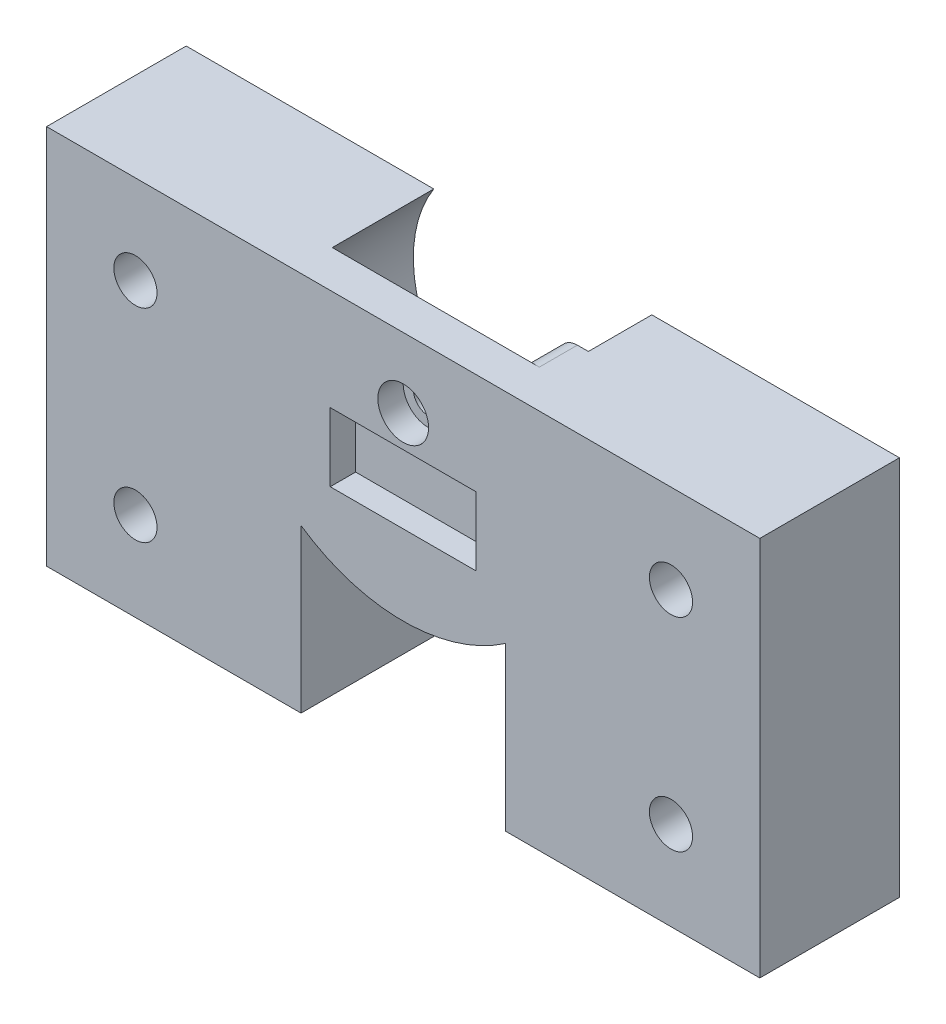
SolidWorks part; units mm, degrees
ref_plane "Front Plane" through (0, 0, 0) normal (0, 0, 1) x (1, 0, 0)
ref_plane "Top Plane" through (0, 0, 0) normal (0, 1, 0) x (1, 0, 0)
ref_plane "Right Plane" through (0, 0, 0) normal (1, 0, 0) x (0, 0, -1)
sketch "Sketch1" plane through (0, 0, 0) normal (0, 0, 1) x (1, 0, 0)
  line L0 (19.5099, 0) -> (0, 0)
  line L1 (28.1, -5.5) -> (28.1, -10) construction
  line L2 (0, 0) -> (0, -30)
  line L3 (0, -30) -> (56.2, -30)
  line L4 (36.6901, 0) -> (56.2, 0)
  line L5 (56.2, 0) -> (56.2, -30)
  line L6 (19.5099, 0) -> (36.6901, 0) construction
  line L7 (35.8259, 0) -> (36.6901, 0)
  line L8 (35.8259, -3) -> (37.9889, -3)
  line L18 (0, -15) -> (56.2, -15) construction
  arc A0 (19.5099, 0) -> (37.9889, -3) centre (28.1, -5.5) ccw
  arc A1 (35.8259, 0) -> (35.8259, -3) centre (35.8259, -1.5) ccw
  dimension "D4" = 30
  dimension "D5" = 1.5
  dimension "D2" = 5.5
  dimension "D1" = 10.2
  dimension "D3" = 56.2
extrude "Boss-Extrude1" add sketch "Sketch1" along normal blind 8
sketch "Sketch2" [suppressed] plane through (0, 0, 0) normal (0, 0, -1) x (-1, 0, 0)
  line L0 (-56.2, -15) -> (0, -15) construction
  line L1 (-56.2, -30) -> (-56.2, 0) construction
  line L2 (-46.0015, -7) -> (-47.6007, -4.23)
  line L3 (-47.6007, -4.23) -> (-50.7993, -4.23)
  line L4 (-50.7993, -4.23) -> (-52.3985, -7)
  line L5 (-52.3985, -7) -> (-50.7993, -9.77)
  line L6 (-50.7993, -9.77) -> (-47.6007, -9.77)
  line L7 (-47.6007, -9.77) -> (-46.0015, -7)
  line L8 (0, 0) -> (0, -30) construction
  line L9 (-8.5993, -9.77) -> (-10.1985, -7)
  line L10 (-28.1, 0) -> (-28.1, -30) construction
  line L11 (0, -30) -> (-56.2, -30) construction
  line L12 (-5.4007, -9.77) -> (-8.5993, -9.77)
  line L13 (-3.8015, -7) -> (-5.4007, -9.77)
  line L14 (-5.4007, -4.23) -> (-3.8015, -7)
  line L15 (-8.5993, -4.23) -> (-5.4007, -4.23)
  line L16 (-10.1985, -7) -> (-8.5993, -4.23)
  line L17 (-10.1985, -23) -> (-8.5993, -25.77)
  line L18 (-8.5993, -25.77) -> (-5.4007, -25.77)
  line L19 (-5.4007, -25.77) -> (-3.8015, -23)
  line L20 (-3.8015, -23) -> (-5.4007, -20.23)
  line L21 (-5.4007, -20.23) -> (-8.5993, -20.23)
  line L22 (-8.5993, -20.23) -> (-10.1985, -23)
  line L23 (-47.6007, -20.23) -> (-46.0015, -23)
  line L24 (-50.7993, -20.23) -> (-47.6007, -20.23)
  line L25 (-52.3985, -23) -> (-50.7993, -20.23)
  line L26 (-50.7993, -25.77) -> (-52.3985, -23)
  line L27 (-47.6007, -25.77) -> (-50.7993, -25.77)
  line L28 (-46.0015, -23) -> (-47.6007, -25.77)
  circle A0 centre (-49.2, -7) radius 2.77 construction
  circle A1 centre (-7, -7) radius 2.77 construction
  circle A2 centre (-7, -23) radius 2.77 construction
  circle A3 centre (-49.2, -23) radius 2.77 construction
  dimension "D1" = 5.54
  dimension "D2" = 7
  dimension "D3" = 7
extrude "Cut-Extrude1" [suppressed] cut sketch "Sketch2" against normal blind 2.4
sketch "Sketch3" plane through (0, 0, 8) normal (0, 0, 1) x (1, 0, 0)
  line L0 (0, 0) -> (0, -30)
  line L1 (0, -30) -> (56.2, -30)
  line L2 (56.2, -30) -> (56.2, 0) construction
  line L3 (56.2, -30) -> (56.2, 0)
  line L4 (0, 0) -> (56.2, 0)
extrude "Boss-Extrude2" add sketch "Sketch3" along normal blind 3
sketch "Sketch4" plane through (0, 0, 0) normal (0, 0, -1) x (-1, 0, 0)
  line L0 (-56.2, -15) -> (0, -15) construction
  line L1 (-56.2, -30) -> (-56.2, 0) construction
  line L2 (0, 0) -> (0, -30) construction
  line L3 (-28.1, -5.5) -> (-28.1, -30) construction
  line L8 (0, -30) -> (-56.2, -30) construction
  circle A0 centre (-49.2, -7) radius 1.7
  circle A1 centre (-7, -7) radius 1.7
  circle A2 centre (-7, -23) radius 1.7
  circle A3 centre (-49.2, -23) radius 1.7
  circle A4 centre (-28.1, -5.5) radius 1.2
  arc A5 (-37.9889, -3) -> (-19.5099, 0) centre (-28.1, -5.5) ccw construction
  dimension "D1" = 3.4
  dimension "D4" = 2.4
  dimension "D2" = 7
  dimension "D3" = 7
extrude "Cut-Extrude2" cut sketch "Sketch4" against normal up to surface (11 mm away) up to face at (28.1, -15, 11)
sketch "Sketch5" plane through (0, 0, 0) normal (0, 0, -1) x (-1, 0, 0)
  line L0 (-19.5099, 0) -> (-36.6901, 0)
  line L1 (-56.2, 0) -> (-35.8259, 0) construction
  arc A0 (-36.6901, 0) -> (-19.5099, 0) centre (-28.1, -5.5) ccw
extrude "Cut-Extrude3" cut sketch "Sketch5" against normal blind 5
sketch "Sketch7" plane through (0, 0, 11) normal (0, 0, 1) x (1, 0, 0)
  line L0 (28.1, -5.5) -> (28.1, -30) construction
  line L1 (22.35, -8) -> (33.85, -8)
  line L2 (22.35, -8) -> (22.35, -13.4)
  line L3 (22.35, -13.4) -> (33.85, -13.4)
  line L4 (33.85, -8) -> (33.85, -13.4)
  line L5 (0, -30) -> (56.2, -30) construction
  circle A0 centre (28.1, -5.5) radius 2
  point P7 (0, 0)
  dimension "D1" = 4
  dimension "D2" = 5.75
  dimension "D3" = 5.4
  dimension "D4" = 8
  dimension "D5" = 5.75
extrude "Cut-Extrude4" cut sketch "Sketch7" against normal blind 2
sketch "Sketch8" plane through (0, 0, 11) normal (0, 0, 1) x (1, 0, 0)
  line L0 (28.1, 0) -> (28.1, -30) construction
  line L1 (56.2, 0) -> (0, 0) construction
  line L2 (0, -30) -> (56.2, -30) construction
  line L3 (0, -15) -> (56.2, -15) construction
  line L4 (0, 0) -> (0, -30) construction
  line L5 (56.2, -30) -> (56.2, 0) construction
  circle A0 centre (7, -7) radius 2.875
  circle A1 centre (49.2, -7) radius 2.875
  circle A2 centre (49.2, -23) radius 2.875
  circle A3 centre (7, -23) radius 2.875
  dimension "D1" = 5.75
extrude "Cut-Extrude5" [suppressed] cut sketch "Sketch8" against normal blind 3
sketch "Sketch9" plane through (0, 0, 0) normal (0, 0, 1) x (1, 0, 0)
  line L0 (23, -30) -> (33.2, -30) construction
  line L1 (0, -30) -> (56.2, -30) construction
  line L2 (33.2, -30) -> (36.15, -30) construction
  line L3 (28.1, -5.5) -> (28.1, -30) construction
  line L4 (36.15, -30) -> (36.15, -17.1978)
  line L5 (36.15, -30) -> (20.05, -30)
  line L6 (23, -30) -> (20.05, -30) construction
  line L7 (20.05, -30) -> (20.05, -17.1978)
  circle A0 centre (28.1, -5.5) radius 14.2 construction
  circle A3 centre (28.1, -5.5) radius 10.2 construction
  arc A4 (20.05, -17.1978) -> (36.15, -17.1978) centre (28.1, -5.5) ccw
  dimension "D1" = 28.4
  dimension "D2" = 20.4
  dimension "D3" = 5.1
  dimension "D4" = 2.95
extrude "Cut-Extrude6" cut sketch "Sketch9" along normal up to next
